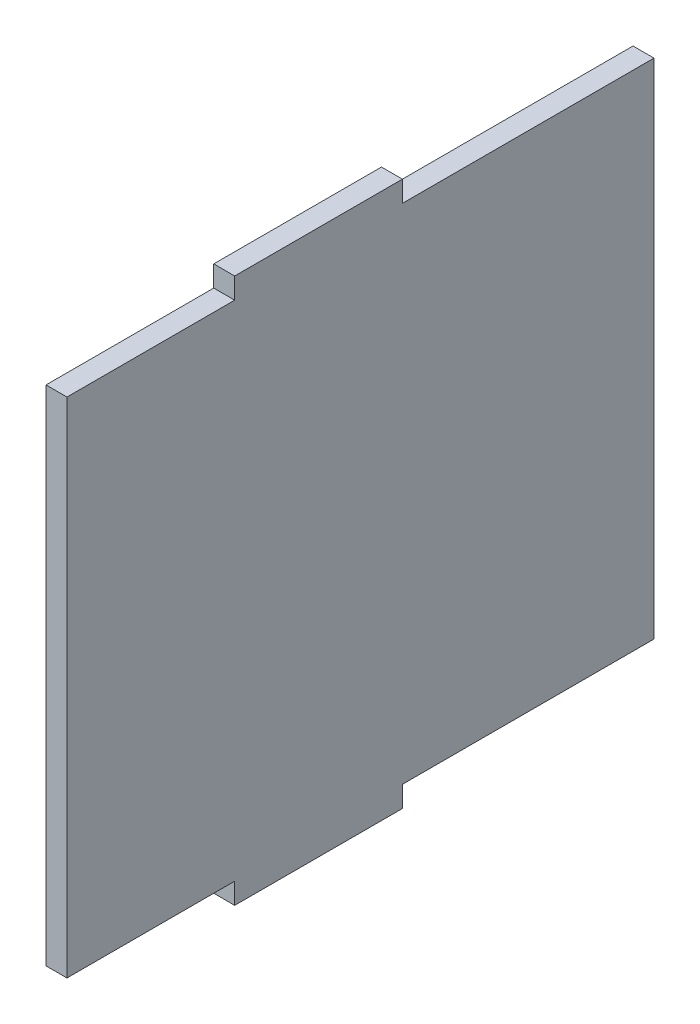
SolidWorks part; units mm, degrees
ref_plane "Front Plane" through (0, 0, 0) normal (0, 0, 1) x (1, 0, 0)
ref_plane "Top Plane" through (0, 0, 0) normal (0, 1, 0) x (1, 0, 0)
ref_plane "Right Plane" through (0, 0, 0) normal (1, 0, 0) x (0, 0, -1)
sketch "Sketch1" plane through (0, 0, 0) normal (1, 0, 0) x (0, 0, -1)
  line L1 (-44.45, -41.275) -> (44.45, -41.275)
  line L2 (-44.45, -41.275) -> (-44.45, 41.275)
  line L3 (-44.45, 41.275) -> (44.45, 41.275)
  line L4 (44.45, -41.275) -> (44.45, 41.275)
  line L5 (-44.45, -41.275) -> (44.45, 41.275) construction
  line L6 (-44.45, 41.275) -> (44.45, -41.275) construction
  point P0 (0, 0)
  dimension "D1" = 88.9
  dimension "D2" = 82.55
extrude "Boss-Extrude1" add sketch "Sketch1" along normal blind 3.175
sketch "Sketch2" plane through (3.175, 0, 0) normal (1, 0, 0) x (0, 0, -1)
  line L0 (-44.45, -41.275) -> (44.45, -41.275) construction
  line L1 (-44.45, -41.275) -> (44.45, -41.275) construction
  line L2 (-19.05, -41.275) -> (-19.05, -38.1) construction
  line L3 (-19.05, 41.275) -> (-19.05, 38.1) construction
  line L4 (44.45, -41.275) -> (6.35, -41.275)
  line L5 (-44.45, 0) -> (44.45, 0) construction
  line L6 (-44.45, 41.275) -> (-44.45, -41.275) construction
  line L7 (44.45, -41.275) -> (44.45, 41.275) construction
  line L8 (44.45, -41.275) -> (44.45, -38.1)
  line L9 (44.45, -38.1) -> (6.35, -38.1)
  line L10 (6.35, -41.275) -> (6.35, -38.1)
  line L11 (-19.05, 38.1) -> (-44.45, 38.1)
  line L12 (0, 41.275) -> (0, -41.275) construction
  line L13 (-19.05, 41.275) -> (-19.05, 38.1)
  line L14 (-19.05, 41.275) -> (-41.275, 41.275)
  line L15 (-44.45, 41.275) -> (-44.45, 38.1)
  line L16 (-44.45, 41.275) -> (-41.275, 41.275)
  line L17 (-44.45, -41.275) -> (-41.275, -41.275)
  line L18 (-44.45, -41.275) -> (-44.45, -38.1)
  line L19 (6.35, 41.275) -> (6.35, 38.1)
  line L20 (44.45, 38.1) -> (6.35, 38.1)
  line L21 (44.45, 41.275) -> (-44.45, 41.275) construction
  line L22 (44.45, 41.275) -> (44.45, 38.1)
  line L23 (44.45, 41.275) -> (6.35, 41.275)
  line L31 (-19.05, -41.275) -> (-41.275, -41.275)
  line L32 (-19.05, -41.275) -> (-19.05, -38.1)
  line L33 (-19.05, -38.1) -> (-44.45, -38.1)
  point P6 (0, -41.275)
  dimension "D1" = 3.175
  dimension "D2" = 19.05
  dimension "D3" = 25.4
extrude "Cut-Extrude1" cut sketch "Sketch2" against normal through all
